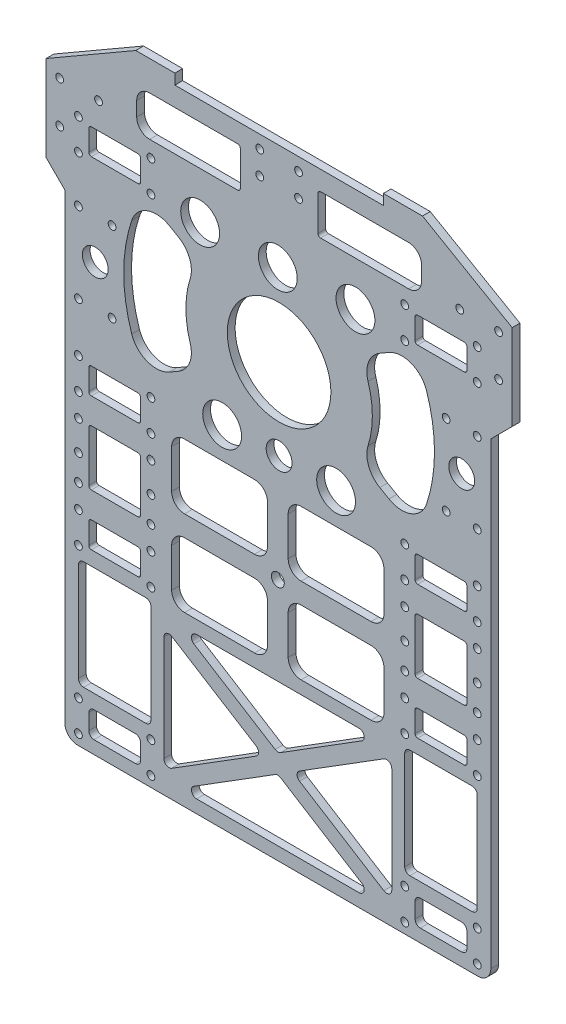
SolidWorks part; units mm, degrees
material "Thornel Mat VMA"
ref_plane "前视基准面" through (0, 0, 0) normal (0, 0, 1) x (1, 0, 0)
ref_plane "上视基准面" through (0, 0, 0) normal (0, 1, 0) x (1, 0, 0)
ref_plane "右视基准面" through (0, 0, 0) normal (1, 0, 0) x (0, 0, -1)
sketch "草图1" plane through (0, 0, 0) normal (0, 0, 1) x (1, 0, 0)
  line L1 (-100.5, 97.5) -> (100.5, 97.5)
  line L2 (-100.5, 97.5) -> (-100.5, -97.5)
  line L3 (-100.5, -97.5) -> (100.5, -97.5)
  line L4 (100.5, 97.5) -> (100.5, -97.5)
  line L5 (-100.5, 97.5) -> (100.5, -97.5) construction
  line L6 (-100.5, -97.5) -> (100.5, 97.5) construction
  point P0 (0, 0)
  dimension "D1" = 195
  dimension "D2" = 201
extrude "凸台-拉伸1" add sketch "草图1" along normal blind 3
sketch "草图13" plane through (0, 0, 0) normal (0, 0, -1) x (-1, 0, 0)
  circle A0 centre (38.7139, -16.7736) radius 1.5
  circle A1 centre (37.905, -10.8284) radius 1.5
  circle A2 centre (35.7357, -1.0665) radius 1.5
  circle A3 centre (33.5664, 8.6954) radius 1.5
  circle A4 centre (-24.7139, -16.7736) radius 1.5
  circle A5 centre (-23.905, -10.8284) radius 1.5
  circle A6 centre (-21.7357, -1.0665) radius 1.5
  circle A7 centre (-19.5664, 8.6954) radius 1.5
  dimension "D1" = 3
chamfer "倒角1" distance 25 angle 60 1 edges at (-100.5, -97.5, 1.5)
sketch "草图14" plane through (0, 0, 0) normal (0, 0, -1) x (-1, 0, 0)
  line L0 (0, 97.5) -> (0, -97.5) construction
  line L1 (-100.5, 97.5) -> (100.5, 97.5) construction
  line L2 (57.1987, -97.5) -> (-100.5, -97.5) construction
  line L3 (57.1987, -97.5) -> (100.5, -72.5) construction
  line L4 (57.1987, -97.5) -> (100.5, -72.5) construction
  line L5 (-57.1987, -97.5) -> (-100.5, -72.5)
  line L6 (-57.1987, -97.5) -> (-100.5, -97.5)
  line L7 (-100.5, -97.5) -> (-100.5, -72.5)
extrude "切除-拉伸6" cut sketch "草图14" against normal blind 10
sketch "草图15" plane through (0, 0, 0) normal (0, 0, -1) x (-1, 0, 0)
  line L0 (34.5, -77.5) -> (34.5, -97.5)
  line L1 (57.1987, -97.5) -> (-57.1987, -97.5) construction
  line L2 (34.5, -97.5) -> (-20.5, -97.5)
  line L3 (-20.5, -97.5) -> (-20.5, -77.5)
  arc A0 (34.5, -77.5) -> (-20.5, -77.5) centre (7, -77.5) ccw
  circle A1 centre (7, -5) radius 20
  dimension "D1" = 40
extrude "切除-拉伸7" cut sketch "草图15" against normal blind 10
sketch "草图16" plane through (0, 0, 0) normal (0, 0, -1) x (-1, 0, 0)
  line L0 (-12.4999, 67.5598) -> (24.5001, 67.5598)
  line L1 (24.5001, 67.5598) -> (24.5001, 97.5)
  line L2 (-100.5, 97.5) -> (100.5, 97.5) construction
  line L3 (24.5001, 97.5) -> (-12.4999, 97.5)
  line L4 (-12.4999, 97.5) -> (-12.4999, 67.5598)
extrude "切除-拉伸9" cut sketch "草图16" against normal blind 10
fillet "圆角1" radius 5 2 edges at (12.4999, 67.5598, 1.5) (-24.5001, 67.5598, 1.5)
fillet "圆角4" radius 10 2 edges at (20.5, -97.5, 1.5) (-34.5, -97.5, 1.5)
sketch "草图17" plane through (0, 0, 3) normal (0, 0, 1) x (1, 0, 0)
  line L0 (-7, -50) -> (-7, 83.4195) construction
  circle A0 centre (0.5, 62.5598) radius 1.5
  circle A1 centre (0.5, 53.5598) radius 1.5
  circle A2 centre (-14.5, 53.5598) radius 1.5
  circle A3 centre (-14.5, 62.5598) radius 1.5
  arc A4 (20.5, -77.5) -> (-34.5, -77.5) centre (-7, -77.5) ccw construction
  dimension "D1" = 3
  dimension "D2" = 3
  dimension "D3" = 3
  dimension "D4" = 3
  dimension "D5" = 9
  dimension "D6" = 9
  dimension "D7" = 7.5
  dimension "D8" = 15
extrude "切除-拉伸10" cut sketch "草图17" against normal blind 5
sketch "草图19" plane through (0, 0, 3) normal (0, 0, 1) x (1, 0, 0)
  line L0 (100.5, -72.5) -> (100.5, 97.5) construction
  line L5 (87.3372, 67.5879) -> (107.3372, 67.5879)
  line L7 (87.3372, 77.5879) -> (107.3372, 77.5879)
  line L9 (100.5, 80.5879) -> (115.5, 80.5879)
  line L10 (100.5, 80.5879) -> (100.5, 64.5879)
  line L11 (100.5, 64.5879) -> (115.5, 64.5879)
  line L12 (115.5, 80.5879) -> (115.5, 64.5879)
  line L13 (-100.5, 97.5) -> (-100.5, -72.5) construction
  line L18 (-88.0649, 74.9622) -> (-108.0649, 74.9622)
  line L20 (-88.0649, 64.9622) -> (-108.0649, 64.9622)
  line L22 (-100.5, 77.9622) -> (-116.5, 77.9622)
  line L23 (-100.5, 77.9622) -> (-100.5, 61.9622)
  line L24 (-100.5, 61.9622) -> (-116.5, 61.9622)
  line L25 (-116.5, 77.9622) -> (-116.5, 61.9622)
  arc A0 (87.3372, 77.5879) -> (87.3372, 67.5879) centre (87.3372, 72.5879) ccw
  arc A2 (107.3372, 67.5879) -> (107.3372, 77.5879) centre (107.3372, 72.5879) ccw
  arc A4 (-88.0649, 64.9622) -> (-88.0649, 74.9622) centre (-88.0649, 69.9622) ccw
  arc A6 (-108.0649, 74.9622) -> (-108.0649, 64.9622) centre (-108.0649, 69.9622) ccw
  dimension "D3" = 10
  dimension "D6" = 15
  dimension "D9" = 10
  dimension "D12" = 10
  dimension "D1" = 16
  dimension "D2" = 16
  dimension "D4" = 10
  dimension "D5" = 20
  dimension "D7" = 3
  dimension "D8" = 16
  dimension "D10" = 10
  dimension "D11" = 20
  dimension "D13" = 3
extrude "凸台-拉伸2" add sketch "草图19" against normal blind 3 contours A2 L5 L10 L11 L12 L9 L7 | L5 A2 L7 L10 | A6 L18 L23 L22 L25 L24 L20 | L18 A6 L20 L23
sketch "草图20" plane through (0, 0, 3) normal (0, 0, 1) x (1, 0, 0)
  line L12 (87.3372, 67.5879) -> (107.3372, 67.5879)
  line L13 (107.3372, 77.5879) -> (87.3372, 77.5879)
  line L18 (87.3372, 67.5879) -> (107.3372, 67.5879)
  line L19 (107.3372, 77.5879) -> (87.3372, 77.5879)
  line L30 (-88.0649, 74.9622) -> (-108.0649, 74.9622)
  line L31 (-108.0649, 64.9622) -> (-88.0649, 64.9622)
  arc A4 (107.3372, 67.5879) -> (107.3372, 77.5879) centre (107.3372, 72.5879) ccw
  arc A5 (87.3372, 77.5879) -> (87.3372, 67.5879) centre (87.3372, 72.5879) ccw
  arc A6 (107.3372, 67.5879) -> (107.3372, 77.5879) centre (107.3372, 72.5879) ccw
  arc A7 (87.3372, 77.5879) -> (87.3372, 67.5879) centre (87.3372, 72.5879) ccw
  arc A10 (-108.0649, 74.9622) -> (-108.0649, 64.9622) centre (-108.0649, 69.9622) ccw
  arc A11 (-88.0649, 64.9622) -> (-88.0649, 74.9622) centre (-88.0649, 69.9622) ccw
extrude "切除-拉伸12" [suppressed] cut sketch "草图20" against normal blind 3 contours L13 A5 L12 A4 | L31 A11 L30 A10
chamfer "倒角3" distance 10 angle 45 4 edges at (-100.5, 61.9622, 1.5) (-100.5, 77.9622, 1.5) (100.5, 80.5879, 1.5) (100.5, 64.5879, 1.5)
sketch "草图27" plane through (0, 0, 3) normal (0, 0, 1) x (1, 0, 0)
  line L0 (100.5, -72.5) -> (100.5, 54.5879) construction
  line L1 (-80.5, 37.5) -> (-60.5, 37.5)
  line L2 (-80.5, 37.5) -> (-80.5, 27.5)
  line L3 (-80.5, 27.5) -> (-60.5, 27.5)
  line L4 (-60.5, 37.5) -> (-60.5, 27.5)
  line L5 (-80.5, 37.5) -> (-60.5, 27.5) construction
  line L6 (-80.5, 27.5) -> (-60.5, 37.5) construction
  line L7 (-80.5, -42.5) -> (-60.5, -42.5)
  line L8 (-80.5, -42.5) -> (-80.5, -52.5)
  line L9 (-80.5, -52.5) -> (-60.5, -52.5)
  line L10 (-60.5, -42.5) -> (-60.5, -52.5)
  line L11 (-80.5, -42.5) -> (-60.5, -52.5) construction
  line L12 (-80.5, -52.5) -> (-60.5, -42.5) construction
  line L13 (45.5, -42.5) -> (65.5, -42.5)
  line L14 (45.5, -42.5) -> (45.5, -52.5)
  line L15 (45.5, -52.5) -> (65.5, -52.5)
  line L16 (65.5, -42.5) -> (65.5, -52.5)
  line L17 (45.5, -42.5) -> (65.5, -52.5) construction
  line L18 (45.5, -52.5) -> (65.5, -42.5) construction
  line L19 (45.5, 37.5) -> (65.5, 37.5)
  line L20 (45.5, 37.5) -> (45.5, 27.5)
  line L21 (45.5, 27.5) -> (65.5, 27.5)
  line L22 (65.5, 37.5) -> (65.5, 27.5)
  line L23 (45.5, 37.5) -> (65.5, 27.5) construction
  line L24 (45.5, 27.5) -> (65.5, 37.5) construction
  line L25 (-100.5, 51.9622) -> (-100.5, -72.5) construction
  line L26 (100.5, 97.5) -> (12.4999, 97.5) construction
  line L27 (-24.5001, 97.5) -> (-100.5, 97.5) construction
  point P0 (-70.5, 32.5)
  point P5 (-70.5, -47.5)
  point P10 (55.5, -47.5)
  point P15 (55.5, 32.5)
  dimension "D1" = 10
  dimension "D2" = 20
  dimension "D3" = 10
  dimension "D4" = 20
  dimension "D5" = 10
  dimension "D6" = 20
  dimension "D7" = 10
  dimension "D8" = 20
  dimension "D9" = 35
  dimension "D10" = 35
  dimension "D11" = 70
  dimension "D12" = 20
  dimension "D13" = 20
  dimension "D14" = 70
  dimension "D15" = 60
  dimension "D16" = 60
extrude "切除-拉伸16" cut sketch "草图27" against normal blind 9
fillet "圆角6" radius 1 16 edges at (45.5, 37.5, 1.5) (45.5, 27.5, 1.5) (65.5, 27.5, 1.5) (65.5, 37.5, 1.5) (65.5, -42.5, 1.5) (45.5, -42.5, 1.5) (45.5, -52.5, 1.5) (65.5, -52.5, 1.5) (-60.5, -52.5, 1.5) (-60.5, -42.5, 1.5) (-80.5, -42.5, 1.5) (-80.5, -52.5, 1.5) (-80.5, 27.5, 1.5) (-60.5, 27.5, 1.5) (-80.5, 37.5, 1.5) (-60.5, 37.5, 1.5)
sketch "草图30" plane through (0, 0, 3) normal (0, 0, 1) x (1, 0, 0)
  line L1 (110.5, 80.5879) -> (4.4959, 80.5879)
  line L2 (110.5, 80.5879) -> (110.5, 104.5128)
  line L3 (110.5, 104.5128) -> (4.4959, 104.5128)
  line L4 (4.4959, 80.5879) -> (4.4959, 104.5128)
  line L5 (-110.5, 77.9622) -> (-16.3342, 77.9622)
  line L6 (-110.5, 77.9622) -> (-110.5, 106.6734)
  line L7 (-110.5, 106.6734) -> (-16.3342, 106.6734)
  line L8 (-16.3342, 77.9622) -> (-16.3342, 106.6734)
  line L9 (-100.5, -72.5) -> (117.3042, -72.5)
  line L10 (-100.5, -72.5) -> (-100.5, -110.8068)
  line L11 (-100.5, -110.8068) -> (117.3042, -110.8068)
  line L12 (117.3042, -72.5) -> (117.3042, -110.8068)
extrude "切除-拉伸18" cut sketch "草图30" against normal blind 10
sketch "草图31" plane through (0, 0, 3) normal (0, 0, 1) x (1, 0, 0)
  line L0 (-116.5, 61.9622) -> (-100.5, 45.9622)
  line L1 (-100.5, 51.9622) -> (-100.5, -72.5) construction
  line L2 (-100.5, 45.9622) -> (-100.5, 51.9622)
  line L3 (-100.5, 51.9622) -> (-110.5, 61.9622)
  line L4 (-110.5, 61.9622) -> (-116.5, 61.9622)
  line L5 (115.5, 64.5879) -> (100.5, 49.5879)
  line L6 (100.5, -72.5) -> (100.5, 54.5879) construction
  line L7 (100.5, 49.5879) -> (100.5, 54.5879)
  line L8 (100.5, 54.5879) -> (110.5, 64.5879)
  line L9 (110.5, 64.5879) -> (115.5, 64.5879)
extrude "凸台-拉伸3" add sketch "草图31" against normal blind 3
fillet "圆角7" radius 2 4 edges at (-116.5, 77.9622, 1.5) (115.5, 80.5879, 1.5) (12.4999, 80.5879, 1.5) (-24.5001, 77.9622, 1.5)
sketch "草图32" plane through (0, 0, 3) normal (0, 0, 1) x (1, 0, 0)
  line L0 (-100.5, -72.5) -> (-100.5, -52.5)
  line L1 (-100.5, 45.9622) -> (-100.5, -72.5) construction
  line L2 (-100.5, -72.5) -> (-40.5, -72.5)
  line L3 (-34.0416, -72.5) -> (-100.5, -72.5) construction
  line L4 (-40.5, -72.5) -> (-100.5, -52.5)
  line L5 (100.5, -72.5) -> (100.5, -52.5)
  line L6 (100.5, -72.5) -> (100.5, 49.5879) construction
  line L9 (100.5, -72.5) -> (26.5, -72.5)
  line L10 (100.5, -72.5) -> (20.0416, -72.5) construction
  line L11 (26.5, -72.5) -> (100.5, -52.5)
  dimension "D1" = 20
  dimension "D2" = 60
  dimension "D3" = 74
extrude "切除-拉伸19" cut sketch "草图32" against normal blind 3
chamfer "倒角4" distance 10 angle 45 2 edges at (20.0416, -72.5, 1.5) (-34.0416, -72.5, 1.5)
fillet "圆角8" radius 5 4 edges at (-30.9923, -64.0605, 1.5) (16.9923, -64.0605, 1.5) (27.5213, -72.224, 1.5) (-41.4632, -72.1789, 1.5)
fillet "圆角9" radius 5 2 edges at (100.5, -52.5, 1.5) (-100.5, -52.5, 1.5)
sketch "草图34" plane through (0, 0, 0) normal (0, 0, -1) x (-1, 0, 0)
  line L0 (6.0001, 67.5598) -> (6.0001, 31.469) construction
  line L5 (-7.4999, 67.5598) -> (19.5001, 67.5598) construction
  line L6 (-14.4999, 80.5879) -> (-113.5, 80.5879) construction
  line L7 (-82.8399, 80.5879) -> (-62.8399, 80.5879)
  line L8 (-82.8399, 80.5879) -> (-82.8399, 95.5879)
  line L9 (-82.8399, 95.5879) -> (-62.8399, 95.5879)
  line L10 (-62.8399, 80.5879) -> (-62.8399, 95.5879)
  line L11 (74.8401, 77.9622) -> (74.8401, 95.5879)
  line L12 (94.8401, 95.5879) -> (74.8401, 95.5879)
  line L13 (94.8401, 77.9622) -> (94.8401, 95.5879)
  line L14 (94.8401, 77.9622) -> (74.8401, 77.9622)
  line L15 (26.5001, 77.9622) -> (114.5, 77.9622) construction
  line L16 (100.5, 77.9622) -> (116.5, 77.9622) construction
  dimension "D1" = 20
  dimension "D2" = 68.84
  dimension "D3" = 15
extrude "凸台-拉伸4" add sketch "草图34" against normal blind 3
fillet "圆角12" radius 10 4 edges at (-94.8401, 77.9622, 1.5) (-74.8401, 77.9622, 1.5) (62.8399, 80.5879, 1.5) (82.8399, 80.5879, 1.5)
sketch "草图35" plane through (0, 0, 0) normal (0, 0, -1) x (-1, 0, 0)
  line L0 (-64.5, 37.5) -> (-46.5, 37.5) construction
  line L2 (-65.5, 28.5) -> (-65.5, 36.5) construction
  line L3 (-45.5, 36.5) -> (-45.5, 28.5) construction
  line L4 (60.5, 28.5) -> (60.5, 36.5) construction
  line L5 (61.5, 37.5) -> (79.5, 37.5) construction
  line L6 (80.5, 36.5) -> (80.5, 28.5) construction
  line L7 (-64.5, -42.5) -> (-46.5, -42.5) construction
  line L8 (-65.5, -51.5) -> (-65.5, -43.5) construction
  line L9 (-45.5, -43.5) -> (-45.5, -51.5) construction
  line L10 (80.5, -43.5) -> (80.5, -51.5) construction
  line L11 (61.5, -42.5) -> (79.5, -42.5) construction
  line L12 (60.5, -51.5) -> (60.5, -43.5) construction
  line L13 (-46.5, 27.5) -> (-64.5, 27.5) construction
  circle A2 centre (-41.5, 38.5) radius 1.5
  circle A4 centre (-41.5, -53.5) radius 1.5
  circle A6 centre (-41.5, -41.5) radius 1.5
  circle A8 centre (-69.5, -41.5) radius 1.5
  circle A10 centre (-69.5, -53.5) radius 1.5
  circle A12 centre (84.5, 38.5) radius 1.5
  circle A14 centre (56.5, 26.5) radius 1.5
  circle A16 centre (56.5, 38.5) radius 1.5
  circle A18 centre (-69.5, 26.5) radius 1.5
  circle A20 centre (-69.5, 38.5) radius 1.5
  circle A22 centre (-41.5, 26.5) radius 1.5
  circle A24 centre (56.5, -53.5) radius 1.5
  circle A26 centre (56.5, -41.5) radius 1.5
  circle A28 centre (84.5, -53.5) radius 1.5
  circle A30 centre (84.5, -41.5) radius 1.5
  circle A32 centre (84.5, 26.5) radius 1.5
  dimension "D1" = 12
  dimension "D2" = 1
  dimension "D4" = 4
  dimension "D5" = 4
  dimension "D6" = 4
  dimension "D7" = 12
  dimension "D8" = 1
  dimension "D9" = 4
  dimension "D10" = 4
  dimension "D11" = 12
  dimension "D12" = 1
  dimension "D13" = 12
  dimension "D14" = 1
  dimension "D15" = 4
  dimension "D16" = 12
  dimension "D17" = 12
  dimension "D18" = 1
  dimension "D19" = 1
  dimension "D21" = 4
  dimension "D22" = 12
  dimension "D23" = 12
  dimension "D24" = 4
  dimension "D25" = 4
  dimension "D26" = 1
  dimension "D27" = 1
  dimension "D28" = 4
  dimension "D29" = 3
  dimension "D30" = 3
  dimension "D31" = 3
  dimension "D32" = 3
  dimension "D33" = 3
  dimension "D34" = 3
  dimension "D35" = 3
  dimension "D36" = 3
  dimension "D37" = 3
  dimension "D38" = 3
  dimension "D39" = 3
  dimension "D40" = 3
  dimension "D41" = 3
  dimension "D42" = 3
  dimension "D43" = 3
  dimension "D44" = 3
  dimension "D45" = 1
  dimension "D46" = 4
  dimension "D47" = 4
  dimension "D48" = 4
  dimension "D49" = 4
  dimension "D20" = 4
extrude "切除-拉伸21" cut sketch "草图35" against normal blind 10
sketch "草图36" [suppressed] plane through (0, 0, 3) normal (0, 0, 1) x (1, 0, 0)
  line L0 (107.3372, 77.5879) -> (87.3372, 77.5879)
  line L1 (87.3372, 67.5879) -> (107.3372, 67.5879)
  line L2 (-108.0649, 64.9622) -> (-88.0649, 64.9622)
  line L3 (-108.0649, 74.9622) -> (-88.0649, 74.9622)
  line L4 (-88.0649, 64.9622) -> (-108.0649, 64.9622)
  arc A0 (87.3372, 77.5879) -> (87.3372, 67.5879) centre (87.3372, 72.5879) ccw
  arc A1 (107.3372, 77.5879) -> (107.3372, 67.5879) centre (107.3372, 72.5879) ccw
  arc A2 (-108.0649, 64.9622) -> (-108.0649, 74.9622) centre (-108.0649, 69.9622) ccw
  arc A3 (-88.0649, 64.9622) -> (-88.0649, 74.9622) centre (-88.0649, 69.9622) ccw
extrude "凸台-拉伸5" [suppressed] add sketch "草图36" against normal blind 3 contours A1 L0 A0 L1 | L2 A3 L3 A2
sketch "草图38" plane through (0, 0, 3) normal (0, 0, 1) x (1, 0, 0)
  line L1 (14.4999, 67.5598) -> (14.4999, 80.5879)
  line L2 (14.4999, 80.5879) -> (52.8399, 80.5879) construction
  line L3 (14.4999, 80.5879) -> (-26.6134, 81.4538)
  line L4 (-26.6134, 81.4538) -> (-26.6134, 67.5598)
  line L5 (-26.6134, 67.5598) -> (14.4999, 67.5598)
extrude "切除-拉伸22" cut sketch "草图38" against normal blind 10
fillet "圆角13" radius 6 2 edges at (14.4999, 67.5598, 1.5) (-26.6134, 67.5598, 1.5)
sketch "草图39" plane through (0, 0, 3) normal (0, 0, 1) x (1, 0, 0)
  line L0 (14.4999, 80.5879) -> (20.4999, 80.5879)
  line L1 (14.4999, 80.5879) -> (52.8399, 80.5879) construction
  line L2 (20.4999, 80.5879) -> (20.4999, 67.5879)
  line L3 (20.4999, 67.5879) -> (-30.7926, 67.5879)
  line L4 (-30.7926, 67.5879) -> (-30.7926, 84.8696)
  line L5 (-30.7926, 84.8696) -> (20.4999, 84.8696)
  line L6 (20.4999, 84.8696) -> (20.4999, 80.5879)
extrude "切除-拉伸23" cut sketch "草图39" against normal blind 10
fillet "圆角14" radius 3 2 edges at (-30.7926, 67.5879, 1.5) (20.4999, 67.5879, 1.5)
sketch "草图40" plane through (0, 0, 3) normal (0, 0, 1) x (1, 0, 0)
  line L0 (-79.5, -52.5) -> (-79.5, -32.5) construction
  line L1 (-79.5, -32.5) -> (-100.5, -32.5) construction
  line L2 (-100.5, 45.9622) -> (-100.5, -48.8962) construction
  line L3 (-60.5, -32.5) -> (100.5, -32.5) construction
  line L4 (-100.5, -32.5) -> (-60.5, -32.5)
  line L5 (-100.5, -32.5) -> (-100.5, 17.5)
  line L6 (-100.5, 17.5) -> (-60.5, 17.5)
  line L7 (-60.5, -32.5) -> (-60.5, 17.5)
  line L8 (100.5, -48.672) -> (100.5, 49.5879) construction
  line L10 (100.5, -32.5) -> (45.5, -32.5)
  line L11 (100.5, -32.5) -> (100.5, 17.5)
  line L12 (100.5, 17.5) -> (45.5, 17.5)
  line L13 (45.5, -32.5) -> (45.5, 17.5)
  dimension "D1" = 50
  dimension "D2" = 40
  dimension "D3" = 50
  dimension "D4" = 55
extrude "切除-拉伸24" cut sketch "草图40" against normal blind 10
sketch "草图41" plane through (0, 0, 3) normal (0, 0, 1) x (1, 0, 0)
  line L0 (100.5, 49.5879) -> (61.3931, 10.4809) construction
  line L1 (100.5, -32.5) -> (85.5, -32.5)
  line L2 (100.5, -32.5) -> (100.5, -72.5)
  line L3 (100.5, -72.5) -> (85.5, -72.5)
  line L4 (85.5, -32.5) -> (85.5, -72.5)
  line L6 (100.5, 17.5) -> (85.5, 17.5)
  line L7 (100.5, 17.5) -> (100.5, 49.59)
  line L8 (100.5, 49.59) -> (85.5, 49.59)
  line L9 (85.5, 17.5) -> (85.5, 49.59)
  dimension "D1" = 40
  dimension "D2" = 15
  dimension "D3" = 32.09
  dimension "D4" = 15
extrude "切除-拉伸25" cut sketch "草图41" against normal blind 10
sketch "草图42" plane through (0, 0, 3) normal (0, 0, 1) x (1, 0, 0)
  line L0 (-27.7926, 67.5879) -> (-87.7926, 67.5879)
  line L1 (-87.7926, 67.5879) -> (-95.5726, 77.9622)
  line L2 (-97.769, 80.8911) -> (-100.2823, 112.193)
  line L3 (-100.2823, 112.193) -> (-22.1864, 105.6395)
  line L4 (-22.1864, 105.6395) -> (-27.7926, 67.5879)
  line L5 (17.4999, 67.5879) -> (92.4999, 67.5879)
  line L6 (92.4999, 67.5879) -> (92.4999, 105.6395)
  line L7 (92.4999, 105.6395) -> (9.6626, 105.6395)
  line L8 (9.6626, 105.6395) -> (17.4999, 67.5879)
  line L9 (-97.769, 80.8911) -> (-104.2464, 83.9856)
  line L10 (-104.2464, 83.9856) -> (-104.8401, 77.9622)
  line L11 (-104.8401, 77.9622) -> (-95.5726, 77.9622)
  arc A0 (-104.8401, 77.9622) -> (-94.8401, 87.9622) centre (-104.8401, 87.9622) ccw construction
extrude "切除-拉伸26" cut sketch "草图42" against normal blind 10
sketch "草图43" plane through (0, 67.5879, 0) normal (0, 1, 0) x (1, 0, 0)
  line L1 (92.4999, 0) -> (-87.7926, 0)
  line L2 (92.4999, 0) -> (92.4999, -3)
  line L3 (92.4999, -3) -> (-87.7926, -3)
  line L4 (-87.7926, 0) -> (-87.7926, -3)
  dimension "D1" = 3
  dimension "D2" = 180.2925
extrude "凸台-拉伸6" add sketch "草图43" along normal blind 4
sketch "草图44" plane through (-87.7926, 0, 0) normal (-1, 0, 0) x (0, 0, 1)
  line L4 (0, 67.5879) -> (3, 67.5879)
  line L5 (3, 67.5879) -> (3, 71.5879)
  line L6 (3, 71.5879) -> (0, 71.5879)
  line L7 (0, 71.5879) -> (0, 67.5879)
  line L8 (0, 67.5879) -> (3, 67.5879)
  line L9 (3, 67.5879) -> (3, 71.5879)
  line L10 (3, 71.5879) -> (0, 71.5879)
  line L11 (0, 71.5879) -> (0, 67.5879)
  dimension "D1" = 0
extrude "凸台-拉伸7" add sketch "草图44" along normal blind 4
sketch "草图45" plane through (0, 0, 0) normal (0, 0, -1) x (-1, 0, 0)
  line L0 (95.5726, 77.9622) -> (90.7923, 71.5879)
  line L1 (-92.4999, 71.5879) -> (90.7923, 71.5879) construction
  line L2 (95.5726, 77.9622) -> (90.7923, 71.5879) construction
  line L3 (90.7923, 71.5879) -> (90.7923, 77.9622)
  line L4 (90.7923, 77.9622) -> (95.5726, 77.9622)
extrude "凸台-拉伸8" add sketch "草图45" against normal blind 3
fillet "圆角17" radius 7 1 edges at (-90.7923, 71.5879, 1.5)
fillet "圆角18" radius 9.01 1 edges at (92.4999, 71.5879, 1.5)
sketch "草图46" plane through (0, 0, 0) normal (0, 0, -1) x (-1, 0, 0)
  line L0 (-8.4999, 67.5598) -> (20.6134, 67.5598) construction
  line L1 (-8, 60.0598) -> (-48, 60.0598) construction
  line L2 (-28, 60.0598) -> (-28, 52.3098) construction
  line L4 (-48, 44.5598) -> (-8, 44.5598)
  line L5 (-48, 44.5598) -> (-48, 60.0598)
  line L6 (-48, 60.0598) -> (-8, 60.0598)
  line L7 (-8, 44.5598) -> (-8, 60.0598)
  line L8 (-48, 44.5598) -> (-8, 60.0598) construction
  line L9 (-48, 60.0598) -> (-8, 44.5598) construction
  line L10 (22, 60.0598) -> (62, 60.0598) construction
  line L11 (42, 60.0598) -> (42, 52.3098) construction
  line L13 (22, 44.5598) -> (62, 44.5598)
  line L14 (22, 44.5598) -> (22, 60.0598)
  line L15 (22, 60.0598) -> (62, 60.0598)
  line L16 (62, 44.5598) -> (62, 60.0598)
  line L17 (22, 44.5598) -> (62, 60.0598) construction
  line L18 (22, 60.0598) -> (62, 44.5598) construction
  circle A0 centre (7, -5) radius 20 construction
  dimension "D1" = 15.5
  dimension "D2" = 40
  dimension "D3" = 15.5
  dimension "D4" = 40
  dimension "D5" = 35
  dimension "D6" = 35
  dimension "D7" = 7.5
  dimension "D8" = 7.5
extrude "切除-拉伸27" cut sketch "草图46" against normal blind 3
fillet "圆角21" radius 60 1 edges at (-100.5, 45.9622, 1.5)
fillet "圆角22" radius 40 1 edges at (85.5, 49.59, 1.5)
sketch "草图47" plane through (0, 0, 0) normal (0, 0, -1) x (-1, 0, 0)
  line L0 (-41.5, 38.5) -> (-41.5, 26.5) construction
  line L1 (-41.5, 26.5) -> (56.5, 26.5) construction
  circle A3 centre (7.5, 26.5) radius 7.5
  circle A4 centre (37.5, 26.5) radius 7.5
  circle A5 centre (-22.4851, 27.4456) radius 7.5
  dimension "D1" = 2
  dimension "D2" = 2
extrude "切除-拉伸28" cut sketch "草图47" against normal blind 3
sketch "草图48" plane through (0, 0, 0) normal (0, 0, -1) x (-1, 0, 0)
  line L0 (-65.5, -51.5) -> (-65.5, -61.9595) construction
  line L1 (-85.5, -56.5541) -> (-29.9232, -71.5748) construction
  line L3 (-65.5, -61.9595) -> (100.8508, -61.9595)
  line L4 (-65.5, -61.9595) -> (-65.5, -77.869)
  line L5 (-65.5, -77.869) -> (100.8508, -77.869)
  line L6 (100.8508, -61.9595) -> (100.8508, -77.869)
  dimension "D1" = 15.9095
  dimension "D2" = 166.3508
extrude "切除-拉伸29" cut sketch "草图48" against normal blind 3
sketch "草图49" plane through (0, 0, 0) normal (0, 0, -1) x (-1, 0, 0)
  line L0 (7, -50) -> (7, -36.2623) construction
  line L1 (7, -36.2623) -> (7, -50) construction
  arc A0 (29.6879, -61.9595) -> (-15.6879, -61.9595) centre (7, -77.5) ccw construction
  circle A1 centre (7, -36.2623) radius 5
  circle A3 centre (29, -36.9537) radius 7.5
  circle A101 centre (-15, -36.9537) radius 7.5
  dimension "D1" = 15
  dimension "D2" = 22
  dimension "D3" = 22
  dimension "D4" = 15
extrude "切除-拉伸30" cut sketch "草图49" against normal blind 3
sketch "草图50" plane through (0, 0, 3) normal (0, 0, 1) x (1, 0, 0)
  line L0 (-80.5, -32.5) -> (-80.5, -64.2373)
  line L1 (-100.5, -32.5) -> (-60.5, -32.5) construction
  line L2 (-80.5, -64.2373) -> (-123.8581, -65.719)
  line L3 (-123.8581, -65.719) -> (-123.8581, -20.8463)
  line L4 (-123.8581, -20.8463) -> (-80.5, -32.5)
  line L5 (85.5, -32.5) -> (65.5, -32.5)
  line L6 (45.5, -32.5) -> (85.5, -32.5) construction
  line L7 (65.5, -32.5) -> (65.5, -80.5354)
  line L8 (65.5, -80.5354) -> (103.4685, -75.6672)
  line L9 (103.4685, -75.6672) -> (85.5, -32.5)
sketch "草图51" plane through (0, 0, 3) normal (0, 0, 1) x (1, 0, 0)
  line L0 (-80.5, 17.5) -> (-80.5, -32.5)
  line L1 (-60.5, 17.5) -> (-100.5, 17.5) construction
  line L2 (-100.5, -32.5) -> (-60.5, -32.5) construction
  line L3 (-80.5, -32.5) -> (-60.5, -32.5)
  line L4 (-60.5, -32.5) -> (-60.5, 17.5)
  line L5 (-60.5, 17.5) -> (-80.5, 17.5)
  line L6 (65.5, 17.5) -> (65.5, -32.5)
  line L7 (85.5, 17.5) -> (45.5, 17.5) construction
  line L8 (45.5, -32.5) -> (85.5, -32.5) construction
  line L9 (65.5, -32.5) -> (45.5, -32.5)
  line L10 (45.5, -32.5) -> (45.5, 17.5)
  line L11 (45.5, 17.5) -> (65.5, 17.5)
extrude "凸台-拉伸9" add sketch "草图51" against normal blind 3
sketch "草图52" plane through (0, 0, 3) normal (0, 0, 1) x (1, 0, 0)
  line L1 (111.3372, 68.5879) -> (103.3372, 68.5879)
  line L2 (111.3372, 68.5879) -> (111.3372, 76.5879)
  line L3 (111.3372, 76.5879) -> (103.3372, 76.5879)
  line L4 (103.3372, 68.5879) -> (103.3372, 76.5879)
  line L5 (111.3372, 68.5879) -> (103.3372, 76.5879) construction
  line L6 (111.3372, 76.5879) -> (103.3372, 68.5879) construction
  line L7 (-104.0649, 65.9622) -> (-112.0649, 65.9622)
  line L8 (-104.0649, 65.9622) -> (-104.0649, 73.9622)
  line L9 (-104.0649, 73.9622) -> (-112.0649, 73.9622)
  line L10 (-112.0649, 65.9622) -> (-112.0649, 73.9622)
  line L11 (-104.0649, 65.9622) -> (-112.0649, 73.9622) construction
  line L12 (-104.0649, 73.9622) -> (-112.0649, 65.9622) construction
  point P0 (107.3372, 72.5879)
  point P5 (-108.0649, 69.9622)
  dimension "D1" = 8
  dimension "D2" = 8
extrude "切除-拉伸31" cut sketch "草图52" against normal blind 10
sketch "草图54" plane through (0, 0, 3) normal (0, 0, 1) x (1, 0, 0)
  line L0 (75.5, -59.2568) -> (75.5, -32.5)
  line L2 (85.5, -56.5541) -> (65.5, -61.9595) construction
  line L3 (65.5, -32.5) -> (85.5, -32.5) construction
  line L4 (-91, -55.6667) -> (-91, -32.5)
  line L5 (-72.1216, -61.9595) -> (-97.0811, -53.6396) construction
  line L6 (-100.5, -32.5) -> (-80.5, -32.5) construction
  line L7 (75.5, -59.2568) -> (85.5, -56.5541)
  line L8 (85.5, -32.5) -> (85.5, -56.5541) construction
  line L9 (85.5, -56.5541) -> (85.5, -32.5)
  line L10 (85.5, -32.5) -> (75.5, -32.5)
  line L11 (-91, -55.6667) -> (-100.5, -52.5)
  line L12 (-100.5, -52.5) -> (-100.5, -32.5)
  line L13 (-100.5, -32.5) -> (-91, -32.5)
  circle A1 centre (-84.5, -41.5) radius 1.5 construction
  dimension "D1" = 6.5
extrude "切除-拉伸33" cut sketch "草图54" against normal blind 10
sketch "草图56" plane through (0, 0, 3) normal (0, 0, 1) x (1, 0, 0)
  line L0 (-97, 17.5) -> (-97, 71.5879)
  line L2 (-140.2931, 94.4739) -> (-140.2931, 17.5)
  line L3 (-140.2931, 17.5) -> (-97, 17.5)
  line L4 (-7, 96.3284) -> (-7, -99.4492) construction
  line L10 (-140.2931, 94.4739) -> (-97, 94.4739)
  line L12 (126.2931, 94.4739) -> (83, 94.4739)
  line L13 (126.2931, 94.4739) -> (126.2931, 17.5)
  line L14 (126.2931, 17.5) -> (83, 17.5)
  line L15 (83, 17.5) -> (83, 94.4739)
  line L18 (-83.8203, 71.5879) -> (-97, 71.5879)
  line L19 (-83.8203, 71.5879) -> (-97, 94.4739)
  dimension "D1" = 90
extrude "切除-拉伸34" cut sketch "草图56" against normal through all
sketch "草图57" plane through (0, 0, 3) normal (0, 0, 1) x (1, 0, 0)
  line L0 (-97, 71.5879) -> (83, 71.5879) construction
  line L1 (-47.25, 75.6159) -> (33.25, 75.6159)
  line L2 (-47.25, 75.6159) -> (-47.25, 67.5598)
  line L3 (-47.25, 67.5598) -> (33.25, 67.5598)
  line L4 (33.25, 75.6159) -> (33.25, 67.5598)
  line L5 (-47.25, 75.6159) -> (33.25, 67.5598) construction
  line L6 (-47.25, 67.5598) -> (33.25, 75.6159) construction
  circle A0 centre (0.5, 62.5598) radius 1.5 construction
  point P0 (-7, 71.5879)
  dimension "D1" = 80.5
  dimension "D2" = 5
extrude "切除-拉伸35" cut sketch "草图57" against normal through all
sketch "草图58" plane through (0, 0, 3) normal (0, 0, 1) x (1, 0, 0)
  line L0 (-7, 76.4414) -> (-7, -65.2102) construction
  line L1 (24.1769, 13) -> (44.9615, 25)
  line L2 (24.1769, -23) -> (44.9615, -35)
  line L3 (-38.1769, -23) -> (-58.9615, -35)
  line L4 (-38.1769, 13) -> (-58.9615, 25)
  arc A0 (44.9615, -35) -> (44.9615, 25) centre (-7, -5) ccw
  arc A1 (-38.1769, 13) -> (-38.1769, -23) centre (-7, -5) ccw
  arc A2 (24.1769, -23) -> (24.1769, 13) centre (-7, -5) ccw
  arc A3 (-58.9615, 25) -> (-58.9615, -35) centre (-7, -5) ccw
  dimension "D1" = 120
  dimension "D2" = 72
  dimension "D3" = 60
  dimension "D4" = 60
extrude "切除-拉伸36" cut sketch "草图58" against normal through all
fillet "圆角25" radius 10 8 edges at (-58.9615, -35, 1.5) (-38.1769, -23, 1.5) (-58.9615, 25, 1.5) (-38.1769, 13, 1.5) (24.1769, -23, 1.5) (44.9615, -35, 1.5) (24.1769, 13, 1.5) (44.9615, 25, 1.5)
extrude "切除-拉伸37" cut sketch "草图59" against normal blind 3
sketch "草图59" plane through (-66.2821, 39.0561, 0) normal (0, 0, -1) x (1, 0, 0)
  circle A6 centre (144.0321, 7.4366) radius 1.5
  circle A7 centre (144.0321, -8.5634) radius 1.5
  circle A8 centre (129.0321, -8.5634) radius 1.5
  circle A9 centre (-10.4679, -8.5634) radius 1.5
  circle A10 centre (-25.4679, -8.5634) radius 1.5
  circle A11 centre (-25.4679, 7.4366) radius 1.5
chamfer "倒角5" distance 20 angle 60 1 edges at (83, 71.5879, 1.5)
chamfer "倒角6" distance 20 angle 60 1 edges at (-97, 71.5879, 1.5)
fillet "圆角26" radius 5 4 edges at (-62, 60.0598, 1.5) (-62, 44.5598, 1.5) (48, 44.5598, 1.5) (48, 60.0598, 1.5)
chamfer "倒角7" distance 10 angle 45 2 edges at (-97, 17.5, 1.5) (83, 17.5, 1.5)
sketch "草图61" plane through (0, 0, 3) normal (0, 0, 1) x (1, 0, 0)
  line L0 (-97, 27.5) -> (-97, -61.9595)
  line L1 (-97, -61.9595) -> (-72.1216, -61.9595)
  line L2 (-72.1216, -61.9595) -> (-91, -55.6667)
  line L3 (-91, -55.6667) -> (-91, -32.5)
  line L4 (-91, -32.5) -> (-80.5, -32.5)
  line L5 (-80.5, -32.5) -> (-80.5, 17.5)
  line L6 (-80.5, 17.5) -> (-87, 17.5)
  line L7 (-87, 17.5) -> (-97, 27.5)
  line L8 (83, 27.5) -> (73, 17.5)
  line L9 (73, 17.5) -> (65.5, 17.5)
  line L10 (65.5, 17.5) -> (65.5, -32.5)
  line L11 (65.5, -32.5) -> (75.5, -32.5)
  line L12 (75.5, -32.5) -> (75.5, -59.2568)
  line L13 (75.5, -59.2568) -> (65.5, -61.9595)
  line L14 (65.5, -61.9595) -> (83, -61.9595)
  line L15 (83, -61.9595) -> (83, 27.5)
  line L16 (-29.6879, -61.9595) -> (15.6879, -61.9595)
  arc A0 (15.6879, -61.9595) -> (-29.6879, -61.9595) centre (-7, -77.5) ccw construction
  arc A1 (15.6879, -61.9595) -> (-29.6879, -61.9595) centre (-7, -77.5) ccw
extrude "凸台-拉伸10" add sketch "草图61" against normal blind 3
sketch "草图62" plane through (0, -61.9595, 0) normal (0, -1, 0) x (1, 0, 0)
  line L4 (-97, 0) -> (83, 0)
  line L5 (83, 0) -> (83, 3)
  line L6 (83, 3) -> (-97, 3)
  line L7 (-97, 3) -> (-97, 0)
  line L8 (-97, 0) -> (83, 0)
  line L9 (83, 0) -> (83, 3)
  line L10 (83, 3) -> (-97, 3)
  line L11 (-97, 3) -> (-97, 0)
  dimension "D1" = 0
extrude "凸台-拉伸11" add sketch "草图62" along normal blind 50
extrude "切除-拉伸38" cut sketch "草图63" against normal through all
sketch "草图63" plane through (-66.2821, 39.0561, 3) normal (0, 0, 1) x (-1, 0, 0)
  line L1 (-131.7821, 143.0156) -> (-111.7821, 143.0156)
  line L2 (-131.7821, 143.0156) -> (-131.7821, 133.0156)
  line L3 (-131.7821, 133.0156) -> (-111.7821, 133.0156)
  line L4 (-111.7821, 143.0156) -> (-111.7821, 133.0156)
  line L5 (-131.7821, 143.0156) -> (-111.7821, 133.0156) construction
  line L6 (-131.7821, 133.0156) -> (-111.7821, 143.0156) construction
  line L7 (-5.7821, 143.0156) -> (14.2179, 143.0156)
  line L8 (-5.7821, 143.0156) -> (-5.7821, 133.0156)
  line L9 (-5.7821, 133.0156) -> (14.2179, 133.0156)
  line L10 (14.2179, 143.0156) -> (14.2179, 133.0156)
  line L11 (-5.7821, 143.0156) -> (14.2179, 133.0156) construction
  line L12 (-5.7821, 133.0156) -> (14.2179, 143.0156) construction
  circle A0 centre (-135.7821, 144.0156) radius 1.5
  circle A1 centre (-135.7821, 132.0156) radius 1.5
  circle A2 centre (-107.7821, 144.0156) radius 1.5
  circle A3 centre (-107.7821, 132.0156) radius 1.5
  circle A4 centre (-9.7821, 144.0156) radius 1.5
  circle A5 centre (-9.7821, 132.0156) radius 1.5
  circle A6 centre (18.2179, 144.0156) radius 1.5
  circle A7 centre (18.2179, 132.0156) radius 1.5
  point P0 (-121.7821, 138.0156)
  point P5 (4.2179, 138.0156)
extrude "切除-拉伸39" cut sketch "草图64" against normal through all
sketch "草图64" plane through (-66.2821, 39.0561, 3) normal (0, 0, 1) x (-1, 0, 0)
  line L5 (30.7179, 151.0156) -> (23.4679, 151.0156)
  line L6 (30.7179, 151.0156) -> (30.7179, 20.5561)
  line L7 (30.7179, 20.5561) -> (23.4679, 20.5561)
  line L8 (23.4679, 151.0156) -> (23.4679, 20.5561)
  line L9 (-149.2821, 151.0156) -> (-141.0321, 151.0156)
  line L10 (-149.2821, 151.0156) -> (-149.2821, 20.5561)
  line L11 (-149.2821, 20.5561) -> (-141.0321, 20.5561)
  line L12 (-141.0321, 151.0156) -> (-141.0321, 20.5561)
extrude "切除-拉伸40" cut sketch "草图65" against normal through all
sketch "草图65" plane through (-66.2821, 39.0561, 3) normal (0, 0, 1) x (-1, 0, 0)
  line L1 (-131.7821, 123.0156) -> (-111.7821, 123.0156)
  line L2 (-131.7821, 123.0156) -> (-131.7821, 101.5561)
  line L3 (-131.7821, 101.5561) -> (-111.7821, 101.5561)
  line L4 (-111.7821, 123.0156) -> (-111.7821, 101.5561)
  line L5 (-131.7821, 123.0156) -> (-111.7821, 101.5561) construction
  line L6 (-131.7821, 101.5561) -> (-111.7821, 123.0156) construction
  line L7 (-5.7821, 123.0156) -> (14.2179, 123.0156)
  line L8 (-5.7821, 123.0156) -> (-5.7821, 101.5561)
  line L9 (-5.7821, 101.5561) -> (14.2179, 101.5561)
  line L10 (14.2179, 123.0156) -> (14.2179, 101.5561)
  line L11 (-5.7821, 123.0156) -> (14.2179, 101.5561) construction
  line L12 (-5.7821, 101.5561) -> (14.2179, 123.0156) construction
  circle A0 centre (-135.7821, 123.0156) radius 1.5
  circle A1 centre (-135.7821, 101.5561) radius 1.5
  circle A2 centre (-107.7821, 123.0156) radius 1.5
  circle A3 centre (-107.7821, 101.5561) radius 1.5
  circle A4 centre (18.2179, 123.0156) radius 1.5
  circle A5 centre (18.2179, 101.5561) radius 1.5
  circle A6 centre (-9.7821, 101.5561) radius 1.5
  circle A7 centre (-9.7821, 123.0156) radius 1.5
  point P0 (-121.7821, 112.2858)
  point P5 (4.2179, 112.2858)
extrude "切除-拉伸41" cut sketch "草图66" against normal through all
sketch "草图66" plane through (-66.2821, 39.0561, 3) normal (0, 0, 1) x (-1, 0, 0)
  line L1 (-135.7821, 61.5561) -> (-123.7822, 61.5561) construction
  line L2 (-135.7821, 61.5561) -> (-135.7821, 30.5561) construction
  line L3 (-135.7821, 30.5561) -> (-123.7822, 30.5561) construction
  line L4 (-123.7822, 61.5561) -> (-123.7822, 30.5561) construction
  line L5 (-135.7821, 61.5561) -> (-123.7822, 30.5561) construction
  line L6 (-135.7821, 30.5561) -> (-123.7822, 61.5561) construction
  line L7 (5.2181, 61.5561) -> (18.2179, 61.5561) construction
  line L8 (5.2181, 61.5561) -> (5.2181, 30.5561) construction
  line L9 (5.2181, 30.5561) -> (18.2179, 30.5561) construction
  line L10 (18.2179, 61.5561) -> (18.2179, 30.5561) construction
  line L11 (5.2181, 61.5561) -> (18.2179, 30.5561) construction
  line L12 (5.2181, 30.5561) -> (18.2179, 61.5561) construction
  circle A2 centre (5.2181, 61.5561) radius 1.5
  circle A3 centre (18.2179, 61.5561) radius 1.5
  circle A4 centre (5.2181, 30.5561) radius 1.5
  circle A5 centre (18.2179, 30.5561) radius 1.5
  circle A6 centre (-135.7821, 30.5561) radius 1.5
  circle A7 centre (-123.7822, 30.5561) radius 1.5
  circle A8 centre (-123.7822, 61.5561) radius 1.5
  circle A9 centre (-135.7821, 61.5561) radius 1.5
  circle A10 centre (-129.7822, 46.0561) radius 5
  circle A11 centre (11.718, 46.0561) radius 5
  point P0 (-129.7822, 46.0561)
  point P5 (11.718, 46.0561)
chamfer "倒角8" distance 8.25 angle 45 1 edges at (74.75, 18.5, 1.5)
chamfer "倒角9" distance 7.25 angle 45 1 edges at (-89.75, 18.5, 1.5)
fillet "圆角27" radius 1 20 edges at (-22, 60.0598, 1.5) (-22, 44.5598, 1.5) (8, 44.5598, 1.5) (8, 60.0598, 1.5) (65.5, -93.9595, 1.5) (65.5, -103.9595, 1.5) (45.5, -103.9595, 1.5) (45.5, -93.9595, 1.5) (-60.5, -93.9595, 1.5) (-60.5, -103.9595, 1.5) (-80.5, -103.9595, 1.5) (-80.5, -93.9595, 1.5) (65.5, -62.5, 1.5) (65.5, -83.9595, 1.5) (45.5, -83.9595, 1.5) (45.5, -62.5, 1.5) (-60.5, -62.5, 1.5) (-60.5, -83.9595, 1.5) (-80.5, -83.9595, 1.5) (-80.5, -62.5, 1.5)
fillet "圆角28" [suppressed] radius 5
sketch "草图67" plane through (0, 0, 0) normal (0, 0, -1) x (-1, 0, 0)
  line L0 (89.75, -111.9595) -> (-74.75, -111.9595) construction
  line L1 (-33.5, -48.9537) -> (48.5, -48.9537)
  line L2 (-33.5, -48.9537) -> (-33.5, -106.9595)
  line L3 (-33.5, -106.9595) -> (48.5, -106.9595)
  line L4 (48.5, -48.9537) -> (48.5, -106.9595)
  line L5 (-33.5, -48.9537) -> (48.5, -106.9595) construction
  line L6 (-33.5, -106.9595) -> (48.5, -48.9537) construction
  line L7 (-33.5, -81.9566) -> (48.5, -81.9566)
  line L8 (-45.5, -63.5) -> (-45.5, -82.9595) construction
  line L9 (60.5, -102.9595) -> (60.5, -94.9595) construction
  line L10 (-33.5, -77.9566) -> (48.5, -77.9566) construction
  line L11 (7.5, -48.9537) -> (7.5, -106.9595) construction
  line L12 (3.5, -48.9537) -> (3.5, -106.9595)
  line L13 (-33.5, -73.9566) -> (48.5, -73.9566)
  line L14 (11.5, -48.9537) -> (11.5, -106.9595)
  circle A0 centre (-15, -36.9537) radius 7.5 construction
  point P0 (7.5, -77.9566)
  dimension "D1" = 5
  dimension "D2" = 12
  dimension "D3" = 12
  dimension "D4" = 12
  dimension "D5" = 4
  dimension "D6" = 4
extrude "切除-拉伸42" cut sketch "草图67" against normal blind 10 contours L2 L13 L12 L1 | L1 L14 L13 L4 | L12 L7 L2 L3 | L7 L14 L3 L4
fillet "圆角29" radius 5 16 edges at (-48.5, -73.9566, 1.5) (-11.5, -73.9566, 1.5) (-11.5, -48.9537, 1.5) (-48.5, -48.9537, 1.5) (33.5, -106.9595, 1.5) (33.5, -81.9566, 1.5) (-3.5, -81.9566, 1.5) (-3.5, -106.9595, 1.5) (-48.5, -106.9595, 1.5) (-11.5, -106.9595, 1.5) (-11.5, -81.9566, 1.5) (-48.5, -81.9566, 1.5) (33.5, -48.9537, 1.5) (-3.5, -73.9566, 1.5) (33.5, -73.9566, 1.5) (-3.5, -48.9537, 1.5)
sketch "草图68" plane through (0, -111.9595, 0) normal (0, -1, 0) x (1, 0, 0)
  line L4 (74.75, 0) -> (74.75, 3)
  line L5 (74.75, 3) -> (-89.75, 3)
  line L7 (-89.75, 0) -> (74.75, 0)
  line L9 (74.75, 3) -> (-89.75, 3)
  line L11 (-89.75, 0) -> (74.75, 0)
  line L16 (74.75, 0) -> (74.75, 3)
  line L18 (-89.75, 3) -> (-89.75, 0)
  line L19 (-89.75, 3) -> (-89.75, 0)
  dimension "D1" = 0
extrude "凸台-拉伸12" add sketch "草图68" along normal blind 60
fillet "圆角31" radius 5 2 edges at (74.75, -171.9595, 1.5) (-89.75, -171.9595, 1.5)
sketch "草图70" plane through (0, 0, 0) normal (0, 0, -1) x (-1, 0, 0)
  line L0 (-1.5, -86.9566) -> (16.5, -68.9566) construction
  circle A0 centre (7.5, -77.9566) radius 2.5
  dimension "D1" = 5
extrude "切除-拉伸44" cut sketch "草图70" against normal blind 10
sketch "草图71" plane through (0, 0, 0) normal (0, 0, -1) x (-1, 0, 0)
  line L0 (84.75, -171.9595) -> (-69.75, -171.9595) construction
  line L1 (51.5, -166.9595) -> (-36.5, -166.9595)
  line L2 (51.5, -166.9595) -> (51.5, -111.9595)
  line L3 (51.5, -111.9595) -> (-36.5, -111.9595)
  line L4 (-36.5, -166.9595) -> (-36.5, -111.9595)
  line L5 (51.5, -166.9595) -> (-36.5, -111.9595) construction
  line L6 (51.5, -111.9595) -> (-36.5, -166.9595) construction
  line L9 (-28.5, -106.9595) -> (-1.5, -106.9595) construction
  line L10 (53.09, -164.4155) -> (-34.91, -109.4155)
  line L11 (49.91, -109.4155) -> (-38.09, -164.4155)
  line L12 (49.91, -169.5035) -> (-38.09, -114.5035)
  line L13 (53.09, -114.5035) -> (-34.91, -169.5035)
  line L14 (89.75, -166.9595) -> (89.75, 11.25) construction
  line L15 (-74.75, 10.25) -> (-74.75, -166.9595) construction
  point P0 (7.5, -139.4595)
  dimension "D1" = 5
  dimension "D2" = 38.25
  dimension "D3" = 38.25
  dimension "D4" = 5
  dimension "D5" = 3
  dimension "D6" = 3
extrude "切除-拉伸45" cut sketch "草图71" against normal blind 3 contours L12 L13 L1 | L11 L12 L4 | L2 L13 L10 | L11 L3 L10
fillet "圆角32" radius 2 12 edges at (36.5, -115.4972, 1.5) (-1.8396, -139.4595, 1.5) (36.5, -163.4217, 1.5) (30.8396, -111.9595, 1.5) (-45.8396, -111.9595, 1.5) (-7.5, -135.9217, 1.5) (-45.8396, -166.9595, 1.5) (-7.5, -142.9972, 1.5) (-51.5, -163.4217, 1.5) (-13.1604, -139.4595, 1.5) (-51.5, -115.4972, 1.5) (30.8396, -166.9595, 1.5)
extrude "切除-拉伸47" cut sketch "草图73" against normal through all
sketch "草图73" plane through (-66.2821, 39.0561, 3) normal (0, 0, 1) x (-1, 0, 0)
  line L1 (-131.7821, 206.0156) -> (-111.7821, 206.0156)
  line L2 (-131.7821, 206.0156) -> (-131.7821, 196.0156)
  line L3 (-131.7821, 196.0156) -> (-111.7821, 196.0156)
  line L4 (-111.7821, 206.0156) -> (-111.7821, 196.0156)
  line L5 (-131.7821, 206.0156) -> (-111.7821, 196.0156) construction
  line L6 (-131.7821, 196.0156) -> (-111.7821, 206.0156) construction
  line L7 (-5.7821, 206.0156) -> (14.2179, 206.0156)
  line L8 (-5.7821, 206.0156) -> (-5.7821, 196.0156)
  line L9 (-5.7821, 196.0156) -> (14.2179, 196.0156)
  line L10 (14.2179, 206.0156) -> (14.2179, 196.0156)
  line L11 (-5.7821, 206.0156) -> (14.2179, 196.0156) construction
  line L12 (-5.7821, 196.0156) -> (14.2179, 206.0156) construction
  line L16 (-135.7821, 207.0156) -> (-107.7821, 207.0156) construction
  line L17 (-135.7821, 207.0156) -> (-135.7821, 195.0156) construction
  line L18 (-135.7821, 195.0156) -> (-107.7821, 195.0156) construction
  line L19 (-107.7821, 207.0156) -> (-107.7821, 195.0156) construction
  line L20 (-135.7821, 207.0156) -> (-107.7821, 195.0156) construction
  line L21 (-135.7821, 195.0156) -> (-107.7821, 207.0156) construction
  line L22 (-9.7821, 207.0156) -> (18.2179, 207.0156) construction
  line L23 (-9.7821, 207.0156) -> (-9.7821, 195.0156) construction
  line L24 (-9.7821, 195.0156) -> (18.2179, 195.0156) construction
  line L25 (18.2179, 207.0156) -> (18.2179, 195.0156) construction
  line L26 (-9.7821, 207.0156) -> (18.2179, 195.0156) construction
  line L27 (-9.7821, 195.0156) -> (18.2179, 207.0156) construction
  line L28 (-135.7821, 190.5156) -> (-107.7821, 190.5156)
  line L29 (-135.7821, 190.5156) -> (-135.7821, 148.5156)
  line L30 (-135.7821, 148.5156) -> (-107.7821, 148.5156)
  line L31 (-107.7821, 190.5156) -> (-107.7821, 148.5156)
  line L32 (-135.7821, 190.5156) -> (-107.7821, 148.5156) construction
  line L33 (-135.7821, 148.5156) -> (-107.7821, 190.5156) construction
  line L34 (-9.7821, 190.5156) -> (18.2179, 190.5156)
  line L35 (-9.7821, 190.5156) -> (-9.7821, 148.5156)
  line L36 (-9.7821, 148.5156) -> (18.2179, 148.5156)
  line L37 (18.2179, 190.5156) -> (18.2179, 148.5156)
  line L38 (-9.7821, 190.5156) -> (18.2179, 148.5156) construction
  line L39 (-9.7821, 148.5156) -> (18.2179, 190.5156) construction
  circle A0 centre (-135.7821, 207.0156) radius 1.5
  circle A1 centre (-135.7821, 195.0156) radius 1.5
  circle A2 centre (-107.7821, 207.0156) radius 1.5
  circle A3 centre (-107.7821, 195.0156) radius 1.5
  circle A4 centre (18.2179, 207.0156) radius 1.5
  circle A5 centre (18.2179, 195.0156) radius 1.5
  circle A6 centre (-9.7821, 207.0156) radius 1.5
  circle A7 centre (-9.7821, 195.0156) radius 1.5
  point P0 (-121.7821, 201.0156)
  point P5 (4.2179, 201.0156)
  point P16 (-121.7821, 201.0156)
  point P21 (4.2179, 201.0156)
  point P34 (-121.7821, 169.5156)
  point P39 (4.2179, 169.5156)
fillet "圆角33" radius 2 16 edges at (65.5, -156.9595, 1.5) (65.5, -166.9595, 1.5) (45.5, -166.9595, 1.5) (45.5, -156.9595, 1.5) (69.5, -109.4595, 1.5) (69.5, -151.4595, 1.5) (41.5, -151.4595, 1.5) (41.5, -109.4595, 1.5) (-56.5, -109.4595, 1.5) (-84.5, -151.4595, 1.5) (-84.5, -109.4595, 1.5) (-60.5, -156.9595, 1.5) (-60.5, -166.9595, 1.5) (-80.5, -166.9595, 1.5) (-80.5, -156.9595, 1.5) (-56.5, -151.4595, 1.5)
extrude "切除-拉伸48" cut sketch "草图74" against normal through all
sketch "草图74" plane through (-66.2821, 39.0561, 3) normal (0, 0, 1) x (-1, 0, 0)
  circle A0 centre (-135.7821, 113.0156) radius 1.5
  circle A1 centre (-107.7821, 113.0156) radius 1.5
  circle A2 centre (-9.7821, 113.0156) radius 1.5
  circle A3 centre (18.2179, 113.0156) radius 1.5
